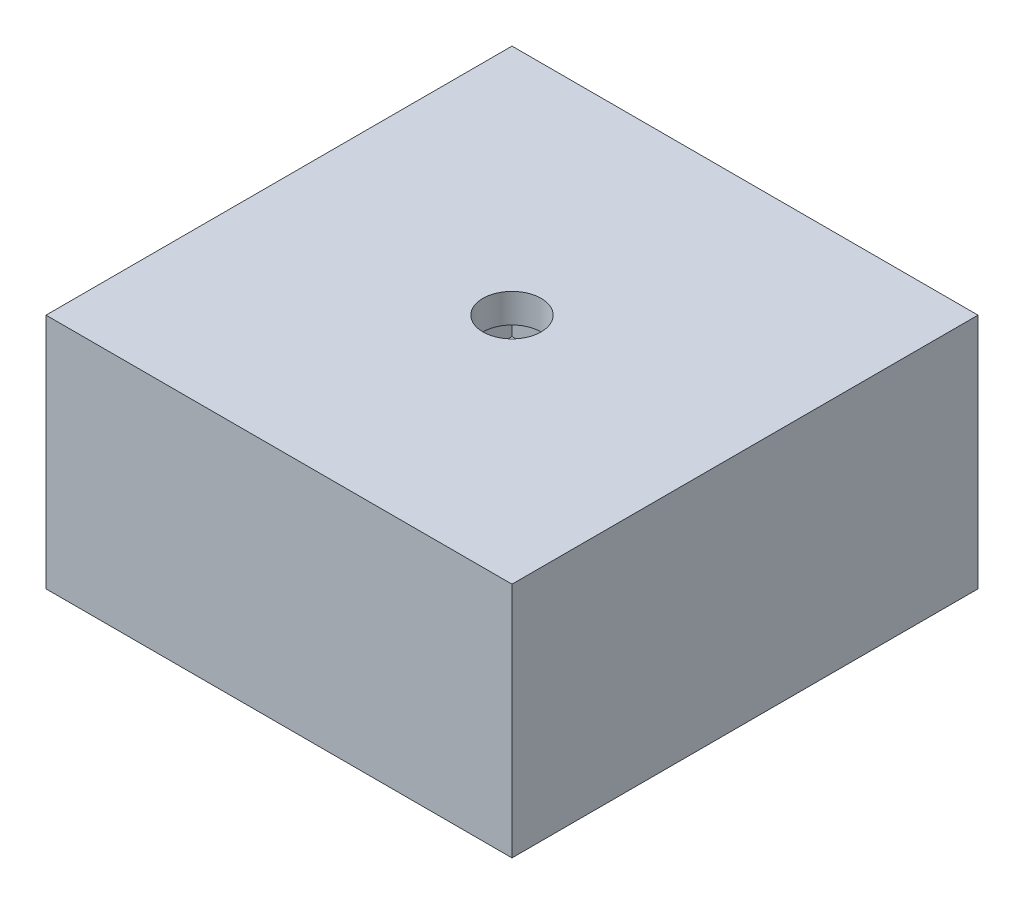
SolidWorks part; units mm, degrees
ref_plane "Front Plane" through (0, 0, 0) normal (0, 0, 1) x (1, 0, 0)
ref_plane "Top Plane" through (0, 0, 0) normal (0, 1, 0) x (1, 0, 0)
ref_plane "Right Plane" through (0, 0, 0) normal (1, 0, 0) x (0, 0, -1)
sketch "Sketch1" plane through (0, 0, 0) normal (0, 1, 0) x (1, 0, 0)
  line L1 (-101.6, -101.6) -> (101.6, -101.6)
  line L2 (-101.6, -101.6) -> (-101.6, 101.6)
  line L3 (-101.6, 101.6) -> (101.6, 101.6)
  line L4 (101.6, -101.6) -> (101.6, 101.6)
  line L5 (-101.6, -101.6) -> (101.6, 101.6) construction
  line L6 (-101.6, 101.6) -> (101.6, -101.6) construction
  line L7 (-95.25, -95.25) -> (95.25, -95.25)
  line L8 (-95.25, -95.25) -> (-95.25, 95.25)
  line L9 (-95.25, 95.25) -> (95.25, 95.25)
  line L10 (95.25, -95.25) -> (95.25, 95.25)
  line L11 (-95.25, -95.25) -> (95.25, 95.25) construction
  line L12 (-95.25, 95.25) -> (95.25, -95.25) construction
  point P0 (0, 0)
  point P6 (0, 0)
  point P11 (96.4715, 96.4715)
  point P12 (-103.65, 103.65)
  dimension "D1" = 203.2
  dimension "D2" = 203.2
  dimension "D3" = 6.35
extrude "Boss-Extrude1" add sketch "Sketch1" along normal blind 90.678
sketch "Sketch2" plane through (0, 90.678, 0) normal (0, 1, 0) x (1, 0, 0)
  line L1 (-101.6, -101.6) -> (101.6, -101.6)
  line L2 (-101.6, -101.6) -> (-101.6, 101.6)
  line L3 (-101.6, 101.6) -> (101.6, 101.6)
  line L4 (101.6, -101.6) -> (101.6, 101.6)
  line L5 (-101.6, -101.6) -> (101.6, 101.6) construction
  line L6 (-101.6, 101.6) -> (101.6, -101.6) construction
  point P0 (0, 0)
extrude "Boss-Extrude2" add sketch "Sketch2" along normal blind 12.7
sketch "Sketch4" plane through (0, 103.378, 0) normal (0, 1, 0) x (1, 0, 0)
  circle A0 centre (0, 0) radius 12.7
  point P2 (59.3505, 62.9475)
  point P3 (0, 0)
  dimension "D1" = 25.4
extrude "Cut-Extrude3" cut sketch "Sketch4" against normal through all
